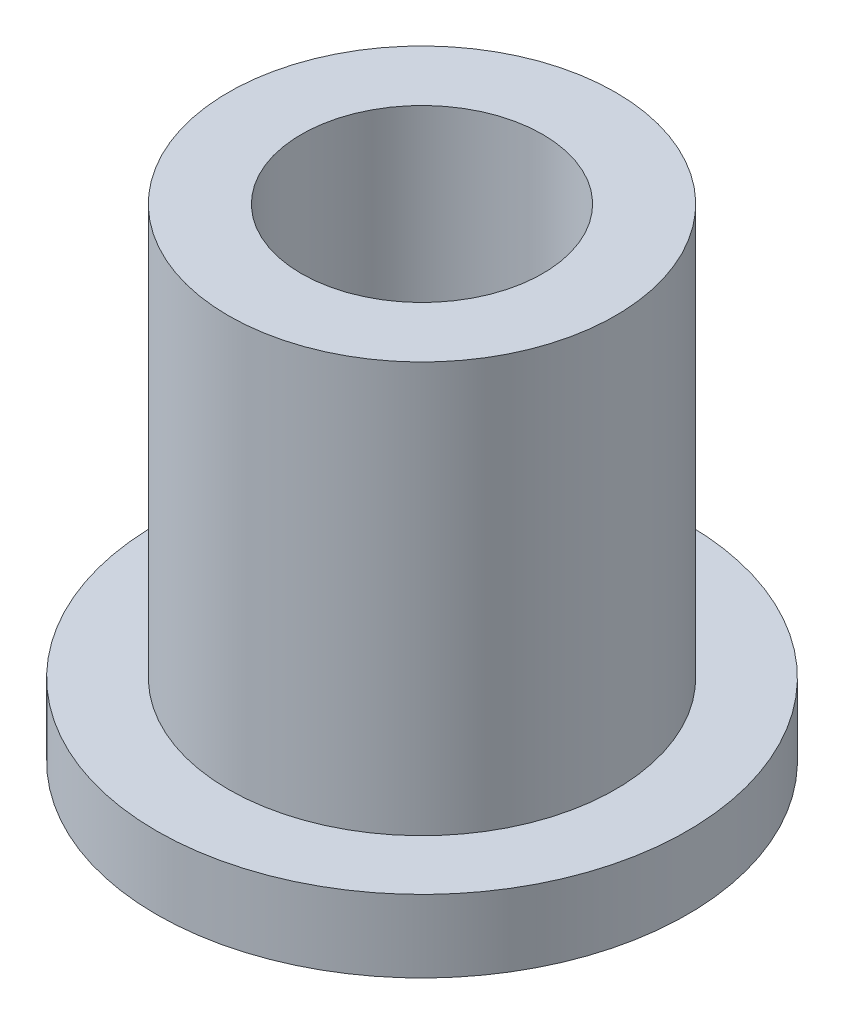
SolidWorks part; units mm, degrees
ref_plane "Front" through (0, 0, 0) normal (0, 0, 1) x (1, 0, 0)
ref_plane "Top" through (0, 0, 0) normal (0, 1, 0) x (1, 0, 0)
ref_plane "Right" through (0, 0, 0) normal (1, 0, 0) x (0, 0, -1)
sketch "Sketch1" plane through (0, 0, 0) normal (0, 1, 0) x (1, 0, 0)
  circle A0 centre (0, 0) radius 2.5
  circle A1 centre (0, 0) radius 4.01
  circle A2 centre (0, 0) radius 5.5
  dimension "ID" = 5
  dimension "OD" = 8.02
  dimension "FlangeOD" = 11
sketch "Sketch2" plane through (0, 0, 0) normal (0, 1, 0) x (1, 0, 0)
  circle A0 centre (0, 0) radius 2.5 construction
  circle A1 centre (0, 0) radius 4.01 construction
  circle A2 centre (0, 0) radius 2.5
  circle A3 centre (0, 0) radius 4.01
extrude "Boss-Extrude1" add sketch "Sketch2" along normal blind 10
sketch "Sketch3" plane through (0, 0, 0) normal (0, 1, 0) x (1, 0, 0)
  circle A0 centre (0, 0) radius 5.5 construction
  circle A1 centre (0, 0) radius 4.01 construction
  circle A2 centre (0, 0) radius 5.5
  circle A3 centre (0, 0) radius 4.01
extrude "Boss-Extrude2" add sketch "Sketch3" along normal blind 1.5
ref_axis "Center Axis 1" through (0, 10, 0) along (0, -1, 0)
